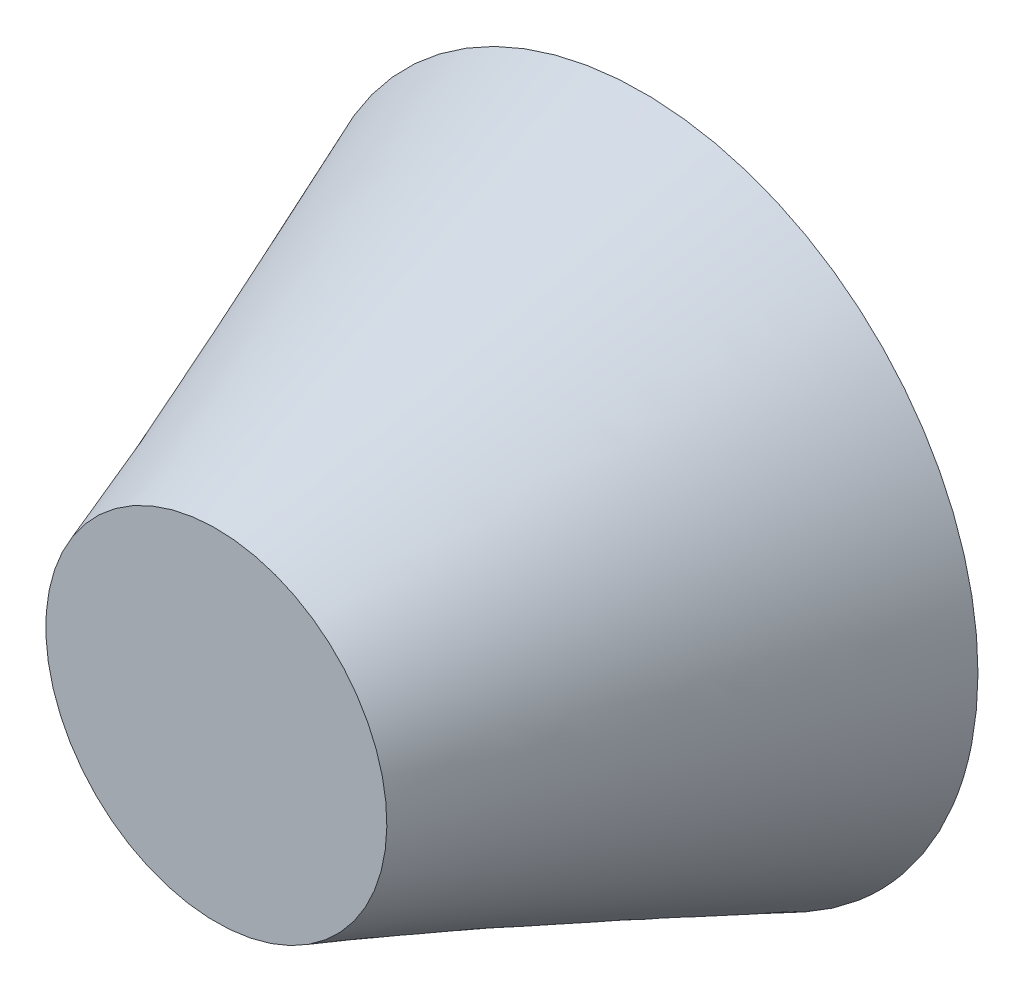
SolidWorks part; units mm, degrees
ref_plane "Piano frontale" through (0, 0, 0) normal (0, 0, 1) x (1, 0, 0)
ref_plane "Piano superiore" through (0, 0, 0) normal (0, 1, 0) x (1, 0, 0)
ref_plane "Piano destro" through (0, 0, 0) normal (1, 0, 0) x (0, 0, -1)
sketch "Schizzo1" plane through (0, 0, 0) normal (0, 0, 1) x (1, 0, 0)
  circle A0 centre (0, 0) radius 11.8
  dimension "D1" = 23.6
ref_plane "Piano1" through (0, 0, 15) normal (0, 0, 1) x (1, 0, 0)
sketch "Schizzo2" plane through (0, 0, 15) normal (0, 0, 1) x (1, 0, 0)
  circle A0 centre (0, 0) radius 6
  dimension "D1" = 12
loft "Loft1" add profiles "Schizzo2", "Schizzo1" connector at (-5.8821, 1.1835, 15) connector at (-10.1605, 6.0003, 0)
sketch "Schizzo3" plane through (0, 0, 0) normal (0, 0, -1) x (-1, 0, 0)
  circle A0 centre (0, 0) radius 9.8
  circle A1 centre (0, 0) radius 11.8 construction
  dimension "D1" = 2
extrude "Taglio-Estrusione1" cut sketch "Schizzo3" against normal blind 0.5
chamfer "Smusso1" distance 0.5 angle 45 1 edges at (-9.8, 0, 0)
